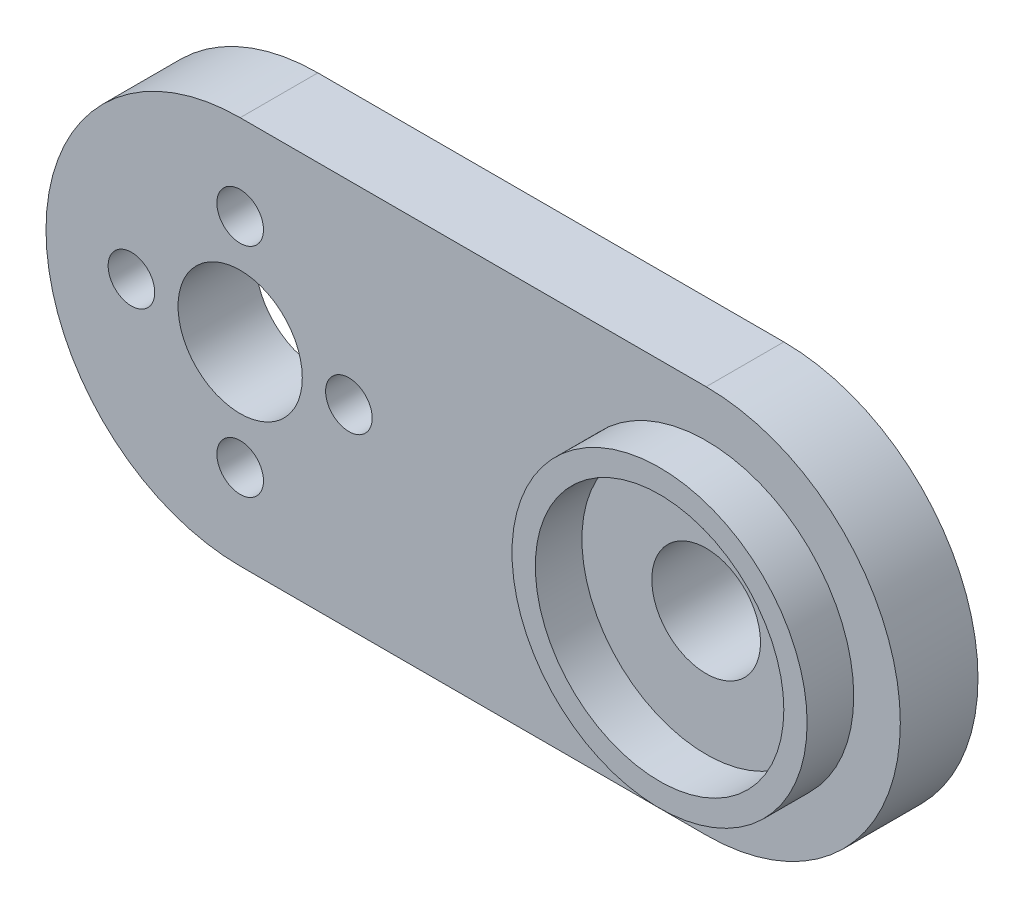
SolidWorks part; units mm, degrees
ref_plane "Front Plane" through (0, 0, 0) normal (0, 0, 1) x (1, 0, 0)
ref_plane "Top Plane" through (0, 0, 0) normal (0, 1, 0) x (1, 0, 0)
ref_plane "Right Plane" through (0, 0, 0) normal (1, 0, 0) x (0, 0, -1)
sketch "Sketch1" plane through (0, 0, 0) normal (0, 0, 1) x (1, 0, 0)
  line L1 (0, 0) -> (30, 0)
  line L2 (0, 0) -> (0, 25)
  line L3 (0, 25) -> (30, 25)
  line L4 (30, 0) -> (30, 25)
  line L5 (30, 15) -> (30, 10)
  circle A0 centre (0, 12.5) radius 12.5
  circle A4 centre (30, 12.5) radius 12.5
  dimension "D1" = 25
  dimension "D4" = 30
extrude "Boss-Extrude2" add sketch "Sketch1" along normal blind 5 contours L2 L1 L4 L3 | A0 | A4
sketch "Sketch3" plane through (0, 0, 5) normal (0, 0, 1) x (1, 0, 0)
  line L0 (0, 0) -> (30, 0) construction
  line L1 (0, 25) -> (30, 25) construction
  line L2 (0, 0) -> (30, 0) construction
  line L3 (0, 25) -> (30, 25) construction
  line L4 (0, 5.5) -> (0, 19.5)
  line L5 (-7, 12.5) -> (7, 12.5)
  arc A0 (30, 0) -> (30, 25) centre (30, 12.5) ccw construction
  arc A1 (0, 25) -> (0, 0) centre (0, 12.5) ccw construction
  arc A2 (30, 0) -> (30, 25) centre (30, 12.5) ccw construction
  arc A3 (0, 25) -> (0, 0) centre (0, 12.5) ccw construction
  circle A4 centre (0, 12.5) radius 4
  circle A5 centre (30, 12.5) radius 3.5
  circle A8 centre (30, 12.5) radius 8
  circle A9 centre (30, 12.5) radius 9.5
  circle A10 centre (0, 19.5) radius 1.5
  circle A11 centre (0, 5.5) radius 1.5
  circle A12 centre (-7, 12.5) radius 1.5
  circle A13 centre (7, 12.5) radius 1.5
  point P14 (0, 12.5)
  point P18 (0, 12.5)
  dimension "D1" = 7
  dimension "D2" = 8
  dimension "D3" = 14
  dimension "D4" = 3
  dimension "D5" = 16
  dimension "D6" = 19
  dimension "D7" = 3
  dimension "D9" = 3
  dimension "D10" = 3
  dimension "D8" = 14
extrude "Cut-Extrude3" cut sketch "Sketch3" against normal up to next contours A4 | A5
extrude "Boss-Extrude3" add sketch "Sketch3<3>" along normal blind 3 contours A9 A8 region at (20.7687, 12.5, 5)
sketch "Sketch3<3>" plane through (0, 0, 5) normal (0, 0, 1) x (1, 0, 0) same geometry as "Sketch3"
extrude "Cut-Extrude4" cut sketch "Sketch3<4>" against normal up to next contours A12 | A10 | A13 | A11 region at (-8.4576, 12.5, 5) region at (-1.0307, 20.5307, 5) region at (7, 13.9576, 5) region at (1.0307, 6.5307, 5)
sketch "Sketch3<4>" plane through (0, 0, 5) normal (0, 0, 1) x (1, 0, 0) same geometry as "Sketch3"
equation "\"LinkCrank_Length\"=30"
equation "\"D4@Sketch1\"=\"LinkCrank_Length\""
